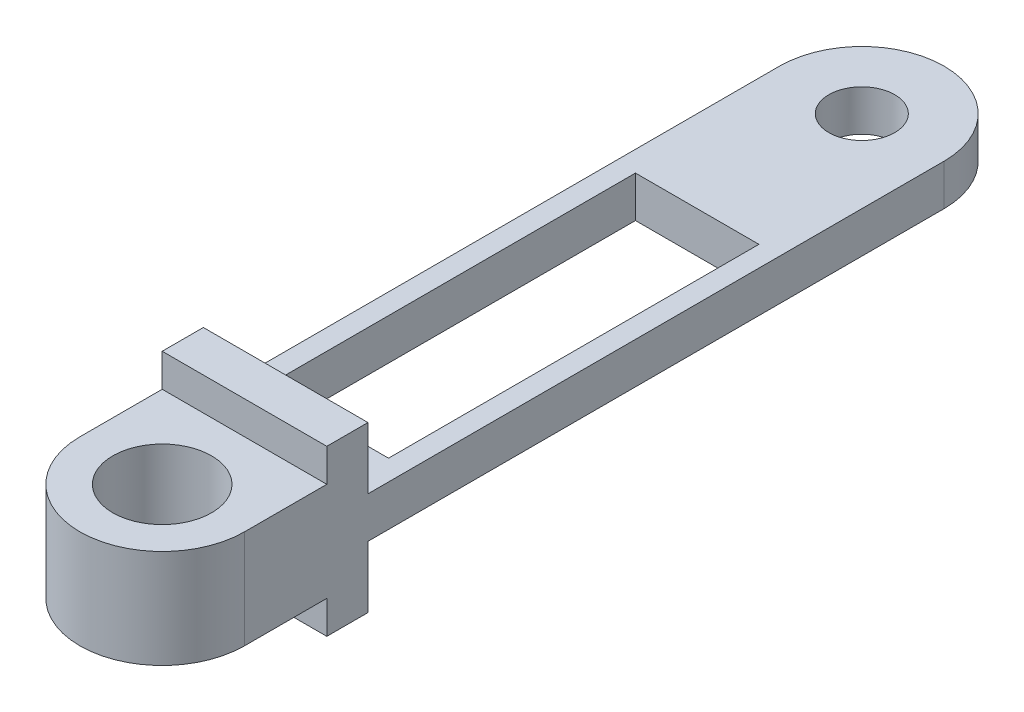
SolidWorks part; units mm, degrees
ref_plane "Front Plane" through (0, 0, 0) normal (0, 0, 1) x (1, 0, 0)
ref_plane "Top Plane" through (0, 0, 0) normal (0, 1, 0) x (1, 0, 0)
ref_plane "Right Plane" through (0, 0, 0) normal (1, 0, 0) x (0, 0, -1)
sketch "草图1" plane through (0, 0, 0) normal (0, 0, 1) x (1, 0, 0)
  line L1 (10, -10) -> (-10, -10)
  line L2 (10, -10) -> (10, 10)
  line L3 (10, 10) -> (-10, 10)
  line L4 (-10, -10) -> (-10, 10)
  line L5 (10, -10) -> (-10, 10) construction
  line L6 (10, 10) -> (-10, -10) construction
  point P0 (0, 0)
  dimension "D1" = 20
  dimension "D2" = 20
extrude "凸台-拉伸1" add sketch "草图1" along normal blind 5
sketch "草图3" plane through (0, 0, 0) normal (0, 1, 0) x (1, 0, 0)
  line L0 (-10, 0) -> (-10, 80)
  line L1 (-10, 80) -> (10, 80)
  line L2 (10, 80) -> (10, 0)
  line L3 (10, -5) -> (10, 0) construction
  line L4 (10, 0) -> (-10, 0) construction
  line L5 (-7.5, 50) -> (7.5, 50)
  line L6 (7.5, 50) -> (7.5, 5)
  line L7 (7.5, 5) -> (-7.5, 5)
  line L8 (-7.5, 5) -> (-7.5, 50)
  line L9 (-10, 0) -> (10, 0)
  point P14 (0, 5)
  dimension "D1" = 80
  dimension "D2" = 20
  dimension "D3" = 15
  dimension "D4" = 45
  dimension "D5" = 5
  dimension "D6" = 10
extrude "凸台-拉伸2" add sketch "草图3" along normal mid plane 5 contours L9 L2 L1 L0 | L5 L6 L7 L8
fillet "圆角1" radius 10 2 edges at (10, 0, -80) (-10, 0, -80)
sketch "草图5" plane through (0, 2.5, 0) normal (0, 1, 0) x (1, 0, 0)
  circle A1 centre (0, 70) radius 4
  dimension "D1" = 8
extrude "切除-拉伸1" cut sketch "草图5" against normal through all
sketch "草图6" plane through (0, 0, 0) normal (0, 1, 0) x (1, 0, 0)
  line L0 (-10, -5) -> (-10, -15)
  line L1 (-10, -5) -> (10, -5)
  line L2 (10, -5) -> (10, -15)
  arc A0 (-10, -15) -> (10, -15) centre (0, -15) ccw
  circle A1 centre (0, -15) radius 6
  dimension "D1" = 10
  dimension "D4" = 12
  dimension "D2" = 10
  dimension "D3" = 20
extrude "凸台-拉伸3" add sketch "草图6" along normal mid plane 12
